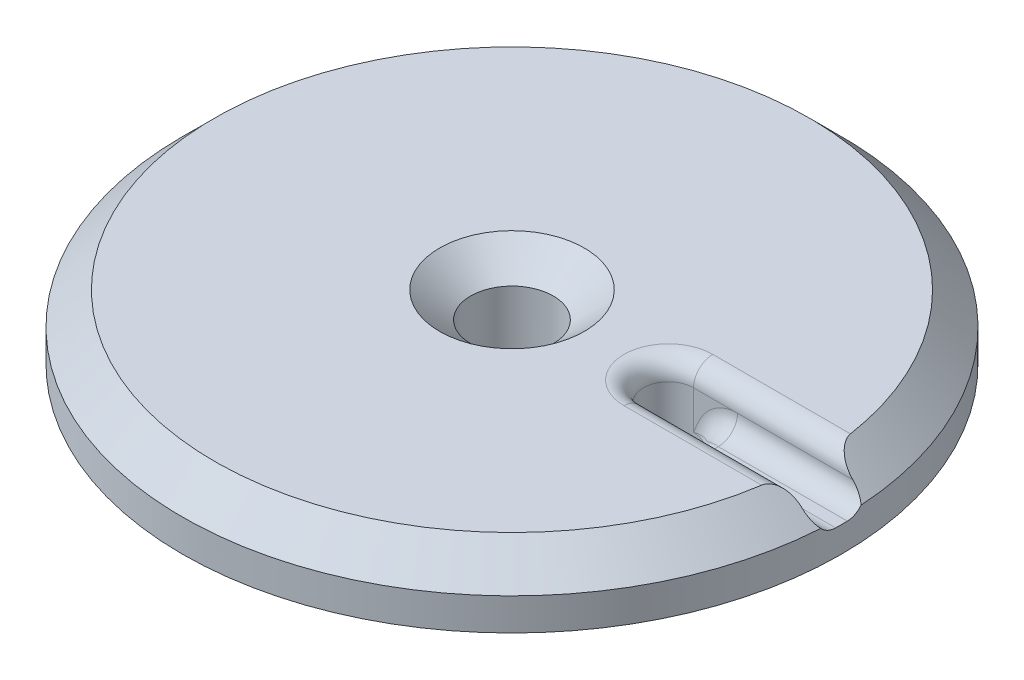
SolidWorks part; units mm, degrees
ref_plane "Front" through (0, 0, 0) normal (0, 0, 1) x (1, 0, 0)
ref_plane "Top" through (0, 0, 0) normal (0, 1, 0) x (1, 0, 0)
ref_plane "Right" through (0, 0, 0) normal (1, 0, 0) x (0, 0, -1)
sketch "Sketch1" plane through (0, 0, 0) normal (0, 1, 0) x (1, 0, 0)
  circle A0 centre (0, 0) radius 13.0175
  dimension "D1" = 26.035
extrude "Boss-Extrude1" add sketch "Sketch1" along normal blind 2.54
chamfer "Chamfer1" distance 1.27 angle 45 1 edges at (0, 2.54, 13.0175)
hole_wizard "CSK for #4 Flat Head Machine Screw (100)1" positions "Sketch2" profile "Sketch3" countersink size "#4" standard "ANSI Inch" end condition through all
sketch "Sketch2" plane through (0, 2.54, 0) normal (0, 1, 0) x (1, 0, 0)
  point P0 (0, 0)
sketch "Sketch3" plane through (0, 2.54, 0) normal (1, 0, 0) x (0, 0, 1)
  line L0 (0, 0) -> (0, 2.54)
  line L1 (0, 2.54) -> (1.6319, 2.54)
  line L2 (1.6319, 2.54) -> (1.6319, 1.0284)
  line L3 (1.6319, 1.0284) -> (2.8575, 0)
  line L5 (2.8575, 0) -> (0, 0)
  line L6 (-1.6319, 1.0284) -> (-2.8575, 0) construction
  line L11 (0, -6.35) -> (0, 107.95) construction
  dimension "Thru Hole Dia." = 3.2639
  dimension "Thru Hole Depth" = 2.54
  dimension "Near C'Sink Dia." = 5.715
  dimension "Near C'Sink Angle" = 100
sketch "Sketch4" plane through (0, 0, 0) normal (0, -1, 0) x (1, 0, 0)
  circle A0 centre (0, 0) radius 10.4775
  circle A1 centre (0, 0) radius 1.6319 construction
  circle A2 centre (0, 0) radius 1.6319
  circle A3 centre (0, 0) radius 13.0175 construction
  dimension "D1" = 2.54
extrude "Boss-Extrude2" add sketch "Sketch4" along normal blind 1.5875
hole_wizard "5/64 (0.07813) Diameter Hole1" positions "Sketch5" profile "Sketch6" hole size "5/64" standard "ANSI Inch" end condition up to next
sketch "Sketch5" plane through (0, 2.54, 0) normal (0, 1, 0) x (1, 0, 0)
  line L0 (6.1791, 0) -> (0, 0) construction
  point P0 (6.1791, 0)
sketch "Sketch6" plane through (6.1791, 2.54, 0) normal (1, 0, 0) x (0, 0, 1)
  line L0 (0, 0) -> (0, 4.1275)
  line L1 (0, 4.1275) -> (0.9923, 4.1275)
  line L2 (0.9923, 4.1275) -> (0.9923, 0)
  line L5 (0.9923, 0) -> (0, 0)
  line L11 (0, -6.35) -> (0, 107.95) construction
  dimension "Thru Hole Dia." = 1.9845
  dimension "Thru Hole Depth" = 4.1275
sketch "Sketch7" plane through (0, 2.54, 0) normal (0, 1, 0) x (1, 0, 0)
  line L1 (6.1791, 0.9923) -> (13.0175, 0.9923)
  line L2 (6.1791, 0.9923) -> (6.1791, -0.9923)
  line L3 (6.1791, -0.9923) -> (13.0175, -0.9923)
  line L4 (13.0175, 0.9923) -> (13.0175, -0.9923)
  circle A0 centre (6.1791, 0) radius 0.9923 construction
  circle A1 centre (0, 0) radius 13.0175 construction
  dimension "D1" = 1.9845
extrude "Cut-Extrude1" cut sketch "Sketch7" against normal blind 1.524
fillet "Fillet2" radius 0.762 1 edges at (7.1713, 1.016, 0)
fillet "Fillet1" radius 0.762 7 edges at (8.9423, 2.54, 0.9923) (5.1868, 2.54, 0) (10.3027, 1.016, 0.9923) (10.3027, 1.016, -0.9923) (8.9423, 2.54, -0.9923) (7.2448, 0.9552, 0.9923) (7.2448, 0.9552, -0.9923)
chamfer "Chamfer2" distance 0.762 angle 45 1 edges at (6.1791, -1.5875, -0.9923)
